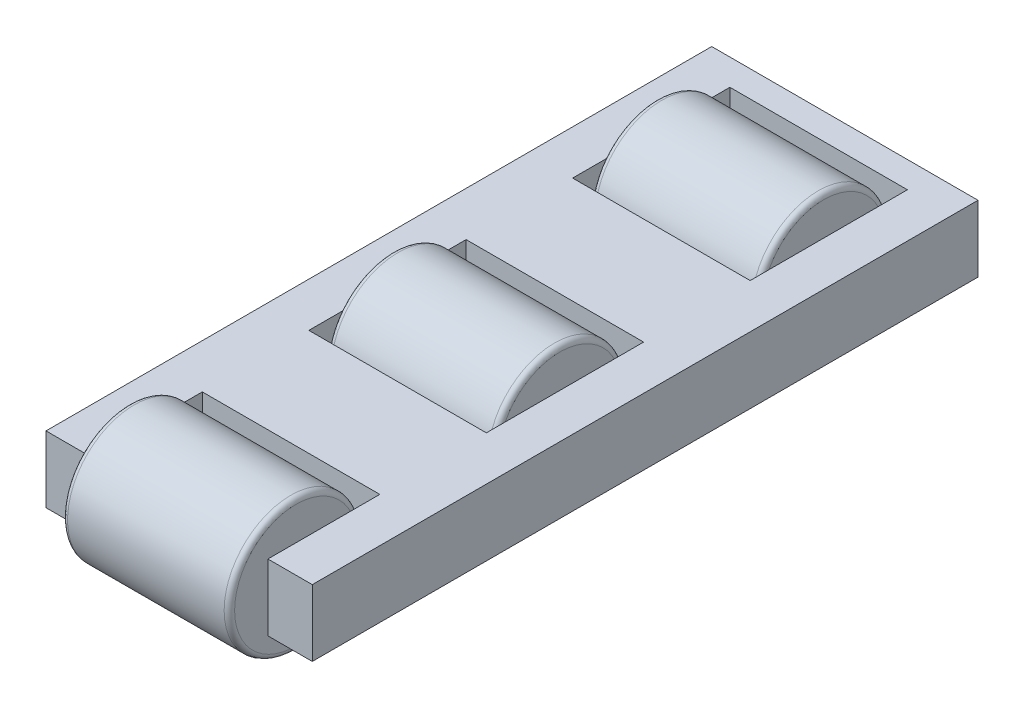
SolidWorks part; units mm, degrees
ref_plane "Front Plane" through (0, 0, 0) normal (0, 0, 1) x (1, 0, 0)
ref_plane "Top Plane" through (0, 0, 0) normal (0, 1, 0) x (1, 0, 0)
ref_plane "Right Plane" through (0, 0, 0) normal (1, 0, 0) x (0, 0, -1)
sketch "Sketch1" plane through (0, 0, 0) normal (0, 1, 0) x (1, 0, 0)
  line L1 (-25.4, -63.5) -> (25.4, -63.5)
  line L2 (-25.4, -63.5) -> (-25.4, 63.5)
  line L3 (-25.4, 63.5) -> (25.4, 63.5)
  line L4 (25.4, -63.5) -> (25.4, 63.5)
  line L5 (-25.4, -63.5) -> (25.4, 63.5) construction
  line L6 (-25.4, 63.5) -> (25.4, -63.5) construction
  point P0 (0, 0)
  dimension "D1" = 127
  dimension "D2" = 50.8
extrude "Boss-Extrude1" add sketch "Sketch1" along normal blind 12.7
sketch "Sketch2" plane through (25.4, 0, 0) normal (1, 0, 0) x (0, 0, -1)
  line L0 (-63.5, 12.7) -> (63.5, 12.7) construction
  line L1 (-63.5, 0) -> (-50.8, 0) construction
  line L2 (-63.5, 0) -> (-63.5, 12.7) construction
  line L3 (-63.5, 12.7) -> (-50.8, 12.7) construction
  line L4 (-50.8, 0) -> (-50.8, 12.7) construction
  line L5 (-63.5, 0) -> (-50.8, 12.7) construction
  line L6 (43.5, 9.8912) -> (63.5, 9.8912) construction
  line L7 (63.5, 12.7) -> (63.5, 0) construction
  line L8 (-57.15, 9.8912) -> (-77.15, 9.8912) construction
  line L9 (-6.825, 12.7) -> (-6.825, 0) construction
  line L10 (-63.5, 0) -> (63.5, 0) construction
  line L11 (43.5, 12.7) -> (43.5, 0) construction
  line L12 (-57.15, 6.35) -> (-6.825, 6.35) construction
  line L13 (-6.825, 6.35) -> (43.5, 6.35) construction
  circle A0 centre (-6.825, 6.35) radius 12.7
  circle A1 centre (43.5, 6.35) radius 12.7
  circle A2 centre (-57.15, 6.35) radius 12.7
  point P13 (-6.825, 6.35)
  point P14 (43.5, 6.35)
  point P18 (-57.15, 6.35)
  dimension "D1" = 25.4
  dimension "D2" = 20
sketch "Sketch3" plane through (0, 12.7, 0) normal (0, 1, 0) x (1, 0, 0)
  line L0 (-25.4, -63.5) -> (-12.7, -63.5) construction
  line L1 (-25.4, -63.5) -> (25.4, -63.5) construction
  line L2 (-12.7, -63.5) -> (0, -63.5) construction
  line L3 (0, -63.5) -> (12.7, -63.5) construction
  line L4 (12.7, -63.5) -> (25.4, -63.5) construction
  line L5 (-25.4, -63.5) -> (-16.9333, -63.5) construction
  line L6 (-16.9333, -63.5) -> (-8.4667, -63.5) construction
  line L7 (-8.4667, -63.5) -> (0, -63.5) construction
  line L8 (0, -63.5) -> (8.4667, -63.5) construction
  line L9 (8.4667, -63.5) -> (16.9333, -63.5) construction
  line L10 (16.9333, -63.5) -> (25.4, -63.5) construction
  line L11 (-16.9333, -63.5) -> (-16.9333, -42.15)
  line L12 (16.9333, -63.5) -> (16.9333, -42.15)
  line L13 (16.9333, -42.15) -> (-16.9333, -42.15)
  line L14 (-16.9333, -63.5) -> (16.9333, -63.5)
  line L15 (-16.9333, 8.175) -> (16.9333, 8.175)
  line L16 (-16.9333, 8.175) -> (-16.9333, -21.825)
  line L17 (-16.9333, -21.825) -> (16.9333, -21.825)
  line L18 (16.9333, 8.175) -> (16.9333, -21.825)
  line L19 (16.9333, 28.5) -> (-16.9333, 28.5)
  line L20 (16.9333, 28.5) -> (16.9333, 58.5)
  line L21 (16.9333, 58.5) -> (-16.9333, 58.5)
  line L22 (-16.9333, 28.5) -> (-16.9333, 58.5)
  point P30 (16.9333, -6.825)
  point P32 (16.9333, 43.5)
  dimension "D1" = 15
  dimension "D2" = 30
extrude "Cut-Extrude1" cut sketch "Sketch3" against normal up to surface (12.7 mm away) up to face at (0, 0, 0)
sketch "Sketch4" plane through (0, 12.7, 0) normal (0, 1, 0) x (1, 0, 0)
  line L0 (12.5526, 28.5) -> (12.5526, 8.175) construction
  line L1 (-16.9333, 28.5) -> (16.9333, 28.5) construction
  line L2 (16.9333, 8.175) -> (-16.9333, 8.175) construction
  line L3 (25.4, -6.825) -> (25.4, 43.5) construction
  line L4 (25.4, 5.6375) -> (17.78, 5.6375)
  line L5 (25.4, 5.6375) -> (25.4, 31.0375)
  line L6 (25.4, 31.0375) -> (17.78, 31.0375)
  line L7 (17.78, 5.6375) -> (17.78, 31.0375)
  line L8 (25.4, 5.6375) -> (17.78, 31.0375) construction
  line L9 (25.4, 31.0375) -> (17.78, 5.6375) construction
  line L10 (9.0274, -21.825) -> (9.0274, -42.15) construction
  line L11 (17.78, -44.6875) -> (25.4, -44.6875)
  line L12 (17.78, -44.6875) -> (17.78, -19.2875)
  line L13 (17.78, -19.2875) -> (25.4, -19.2875)
  line L14 (25.4, -44.6875) -> (25.4, -19.2875)
  line L15 (17.78, -44.6875) -> (25.4, -19.2875) construction
  line L16 (17.78, -19.2875) -> (25.4, -44.6875) construction
  line L17 (-16.9333, -21.825) -> (16.9333, -21.825) construction
  line L18 (16.9333, -42.15) -> (-16.9333, -42.15) construction
  line L19 (25.4, -57.15) -> (25.4, -6.825) construction
  point P6 (9.0274, -31.9875)
  point P7 (21.59, 18.3375)
  point P12 (12.5526, 18.3375)
  point P16 (21.59, -31.9875)
  dimension "D1" = 7.62
  dimension "D2" = 25.4
ref_plane "Plane1" through (15.9333, 0, 0) normal (-1, 0, 0) x (0, 0, 1)
ref_plane "Plane2" through (-15.9333, 0, 0) normal (1, 0, 0) x (0, 0, -1)
sketch "Sketch5" plane through (15.9333, 0, 0) normal (-1, 0, 0) x (0, 0, 1)
  circle A0 centre (6.825, 6.35) radius 12.7
  circle A1 centre (6.825, 6.35) radius 12.7 construction
  circle A2 centre (-43.5, 6.35) radius 12.7
  circle A3 centre (57.15, 6.35) radius 12.7
extrude "Boss-Extrude2" add sketch "Sketch5" along normal up to surface (31.8667 mm away) separate body up to plane "Plane2"
fillet "Fillet1" radius 1 2 edges at (-15.9333, 6.35, -5.875) (15.9333, 6.35, 19.525)
fillet "Fillet2" radius 1 2 edges at (15.9333, 6.35, -30.8) (-15.9333, 6.35, -56.2)
fillet "Fillet3" radius 1 2 edges at (15.9333, 6.35, 69.85) (-15.9333, 6.35, 44.45)
sketch "Sketch6" plane through (0, 12.7, 0) normal (0, 1, 0) x (1, 0, 0)
  line L0 (0, 28.5) -> (0, 8.175) construction
  line L1 (-16.9333, 28.5) -> (16.9333, 28.5) construction
  line L2 (16.9333, 8.175) -> (-16.9333, 8.175) construction
  line L3 (0, -21.825) -> (0, -42.15) construction
  line L4 (-16.9333, -21.825) -> (16.9333, -21.825) construction
  line L5 (16.9333, -42.15) -> (-16.9333, -42.15) construction
  line L7 (16.9333, 28.5) -> (16.9333, 58.5) construction
  line L8 (-16.9333, 58.5) -> (-16.9333, 28.5) construction
  circle A0 centre (16.9333, 18.3375) radius 1.5
  circle A1 centre (-16.9333, 18.3375) radius 1.5
  circle A2 centre (16.9333, -31.9875) radius 1.5
  circle A3 centre (-16.9333, -31.9875) radius 1.5
  point P8 (0, 0)
  point P9 (0, 18.3375)
  point P22 (0, -31.9875)
  point P23 (0, 0)
  point P26 (0, 0)
  dimension "D1" = 3
